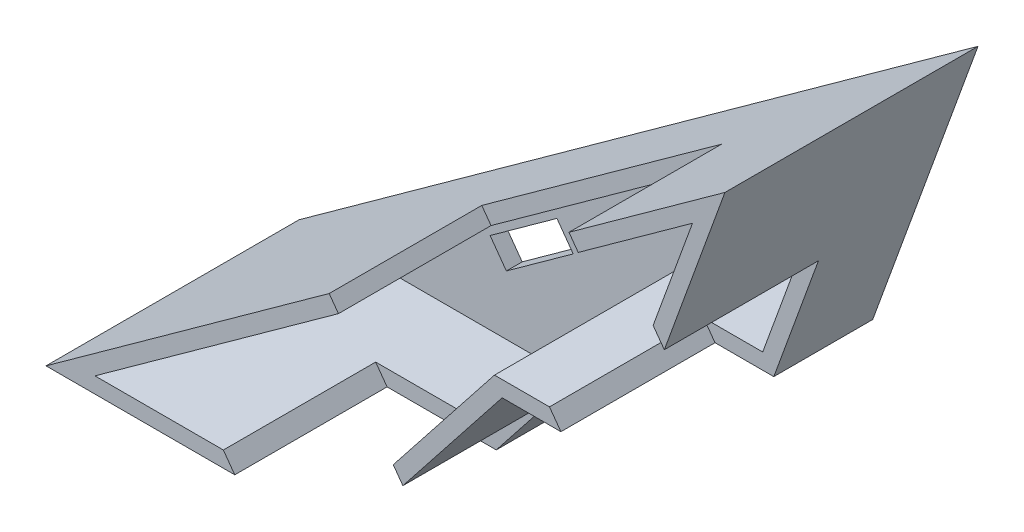
SolidWorks part; units mm, degrees
ref_plane "前视基准面" through (0, 0, 0) normal (0, 0, 1) x (1, 0, 0)
ref_plane "上视基准面" through (0, 0, 0) normal (0, 1, 0) x (1, 0, 0)
ref_plane "右视基准面" through (0, 0, 0) normal (1, 0, 0) x (0, 0, -1)
ref_plane "基准面4" through (0, 0, -30) normal (0, 0, 1) x (1, 0, 0)
sketch "草图2" plane through (0, 0, -30) normal (0, 0, 1) x (1, 0, 0)
  line L0 (134.559, 0.0916) -> (123.9494, -29.0581)
  line L1 (123.9494, -29.0581) -> (109.5193, -29.0581)
  line L2 (109.5193, -29.0581) -> (89.5141, -54.4009)
  line L3 (89.5141, -54.4009) -> (59.0008, -54.4009)
  line L4 (59.0008, -54.4009) -> (134.559, 0.0916)
  line L5 (90.4834, -56.4009) -> (110.7956, -30.6692) construction
  line L6 (125.4914, -30.6692) -> (138.6618, 5.5164) construction
  line L7 (138.6618, 5.5164) -> (52.8085, -56.4009) construction
  line L8 (52.8085, -56.4009) -> (90.4834, -56.4009) construction
  dimension "D1" = 2
  dimension "D2" = 2
  dimension "D3" = 2
  dimension "D4" = 2
ref_plane "基准面5" through (0, 0, 0) normal (0, 0, 1) x (1, 0, 0)
sketch "草图5" plane through (0, 0, 0) normal (0, 0, 1) x (1, 0, 0)
  line L14 (123.9494, -29.0581) -> (134.559, 0.0916)
  line L20 (109.5193, -29.0581) -> (123.9494, -29.0581)
  line L21 (89.5141, -54.4009) -> (109.5193, -29.0581)
  line L22 (59.0008, -54.4009) -> (89.5141, -54.4009)
  line L23 (134.559, 0.0916) -> (59.0008, -54.4009)
  line L24 (123.9494, -29.0581) -> (134.559, 0.0916)
  line L25 (109.5193, -29.0581) -> (123.9494, -29.0581)
  line L26 (89.5141, -54.4009) -> (109.5193, -29.0581)
  line L27 (59.0008, -54.4009) -> (89.5141, -54.4009)
  line L28 (134.559, 0.0916) -> (59.0008, -54.4009)
  dimension "D1" = 0
loft "放样2" add profiles "草图5", "草图2" connector at (123.9494, -29.0581, 0) connector at (123.9494, -29.0581, -30)
shell "抽壳3" thickness 2 removed face at (103.3085, -33.3653, 0) outward yes
sketch "草图10" plane through (45.9973, -63.779, 0) normal (0.5849, -0.8111, 0) x (0.8111, 0.5849, 0)
  line L0 (29.2007, 0) -> (29.2007, -19.2614)
  line L1 (59.11, 0) -> (-59.11, 0) construction
  line L2 (29.2007, -19.2614) -> (51.9661, -19.2614)
  line L3 (51.9661, -19.2614) -> (51.9661, 0)
  line L5 (71.4471, 0) -> (83.5006, 0) construction
  line L6 (77.4738, 0) -> (77.4738, -19.489)
  line L7 (77.4738, -19.489) -> (97.1555, -19.489)
  line L8 (97.1555, -19.489) -> (97.1555, 0)
  line L9 (83.5006, 0) -> (115.6917, 0) construction
  line M4 (109.1908, 0) -> (16.0324, 0)
  line M8 (109.1908, 0) -> (16.0324, 0)
extrude "切除-拉伸8" cut sketch "草图10" along normal blind 49 contours L2 L3 L0 M4 | L7 L8 L6 M8 region at (78.9135, -40.0399, -9.6307) region at (116.8159, -12.7048, -9.7445)
sketch "草图9" plane through (44.8274, -62.1569, 0) normal (-0.5849, 0.8111, 0) x (0.8111, 0.5849, 0)
  line L0 (53.9914, 0) -> (53.9914, 19.2971)
  line L1 (115.6917, 0) -> (9.8401, 0) construction
  line L2 (53.9914, 19.2971) -> (91.376, 19.2971)
  line L3 (91.376, 19.2971) -> (91.376, 0)
  line M7 (9.8401, 0) -> (115.6917, 0)
extrude "切除-拉伸5" cut sketch "草图9" against normal blind 10 contours L3 L2 L0 M7 region at (103.7792, -19.6409, -9.6486)
sketch "草图13" plane through (0, 0, -30) normal (0, 0, 1) x (1, 0, 0)
  line L0 (78.9639, -44.0483) -> (81.0234, -46.9039)
  line L1 (78.9639, -44.0483) -> (87.4171, -37.9519)
  line L2 (81.0234, -46.9039) -> (89.4765, -40.8075)
  line L3 (87.4171, -37.9519) -> (89.4765, -40.8075)
  line L4 (103.8801, -22.9555) -> (118.2257, -12.6095)
  line L5 (103.8801, -22.9555) -> (106.7476, -26.9315)
  line L6 (118.2257, -12.6095) -> (121.0932, -16.5855)
  line L7 (106.7476, -26.9315) -> (121.0932, -16.5855)
  line L9 (134.559, 0.0916) -> (59.0008, -54.4009) construction
extrude "切除-拉伸10" cut sketch "草图13" against normal blind 49
